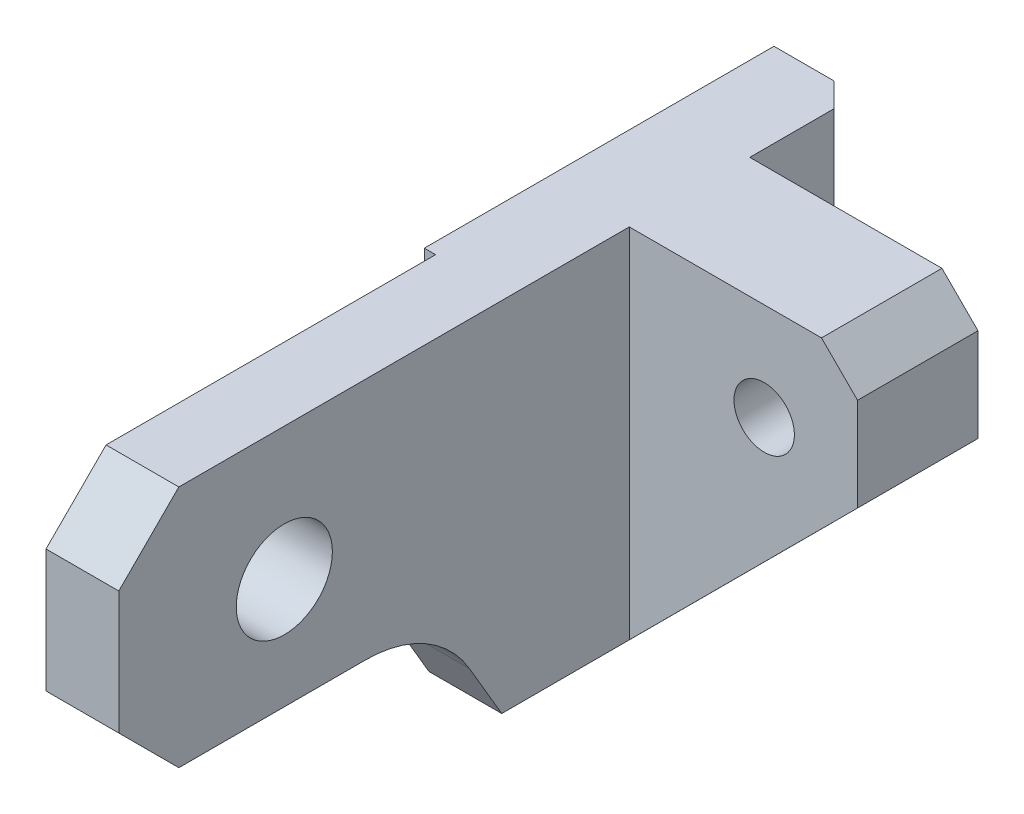
SolidWorks part; units mm, degrees
ref_plane "Спереди" through (0, 0, 0) normal (0, 0, 1) x (1, 0, 0)
ref_plane "Сверху" through (0, 0, 0) normal (0, 1, 0) x (1, 0, 0)
ref_plane "Справа" through (0, 0, 0) normal (1, 0, 0) x (0, 0, -1)
sketch "Эскиз1" plane through (0, 0, 0) normal (1, 0, 0) x (0, 0, -1)
  line L0 (-2.5685, -29.7759) -> (-8.1599, -20.2425)
  line L1 (27.0957, 0) -> (-34.4479, 0)
  line L2 (27.0957, 0) -> (27.0957, -29.7759)
  line L3 (-2.5685, -29.7759) -> (27.0957, -29.7759)
  line L4 (-34.4479, 0) -> (-34.4479, -20.2425)
  line L5 (-8.1599, -20.2425) -> (-34.4479, -20.2425)
extrude "Вытянуть1" add sketch "Эскиз1" against normal blind 7
fillet "Скругление1" radius 10 1 edges at (-3.5, -20.2425, 8.1599)
chamfer "Фаска1" distance 5 angle 45 2 edges at (-3.5, 0, 34.4479) (-3.5, -20.2425, 34.4479)
sketch "Эскиз3" plane through (0, 0, 0) normal (0, 1, 0) x (1, 0, 0)
  line L1 (-9.3151, -2.0159) -> (-6.0604, -2.0159)
  line L2 (-9.3151, -2.0159) -> (-9.3151, -56.1236)
  line L3 (-9.3151, -56.1236) -> (-6.0604, -56.1236)
  line L4 (-6.0604, -2.0159) -> (-6.0604, -56.1236)
extrude "Вырез-Вытянуть2" cut sketch "Эскиз3" against normal through all
sketch "Эскиз4" plane through (0, 0, 0) normal (1, 0, 0) x (0, 0, -1)
  circle A0 centre (-20.6685, -11.0467) radius 4
extrude "Вырез-Вытянуть3" cut sketch "Эскиз4" against normal through all
sketch "Эскиз5" plane through (0, 0, 0) normal (1, 0, 0) x (0, 0, -1)
  line L0 (27.0957, 0) -> (-29.4479, 0) construction
  line L1 (18.0789, -29.7712) -> (8.0502, -29.7712)
  line L2 (18.0789, -29.7712) -> (18.0789, 0)
  line L3 (18.0789, 0) -> (8.0502, 0)
  line L4 (8.0502, -29.7712) -> (8.0502, 0)
extrude "Вытянуть2" add sketch "Эскиз5" along normal blind 19
chamfer "Фаска3" distance 19 angle 45 1 edges at (19, -29.7712, -13.0646)
chamfer "Фаска4" distance 3 angle 45 1 edges at (19, 0, -13.0646)
sketch "Эскиз6" plane through (0, 0, -18.0789) normal (0, 0, -1) x (-1, 0, 0)
  circle A0 centre (-11.2293, -8.118) radius 2.5142
extrude "Вырез-Вытянуть4" cut sketch "Эскиз6" against normal through all
chamfer "Фаска5" distance 2 angle 45 1 edges at (0, -14.8879, -27.0957)
